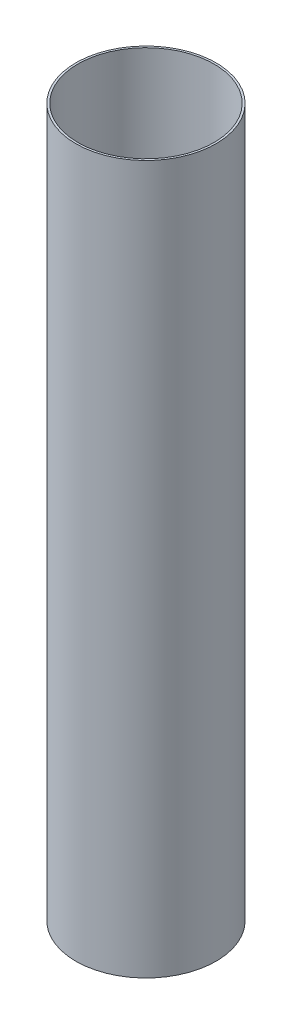
SolidWorks part; units mm, degrees
ref_plane "Front Plane" through (0, 0, 0) normal (0, 0, 1) x (1, 0, 0)
ref_plane "Top Plane" through (0, 0, 0) normal (0, 1, 0) x (1, 0, 0)
ref_plane "Right Plane" through (0, 0, 0) normal (1, 0, 0) x (0, 0, -1)
sketch "Sketch1" plane through (0, 0, 0) normal (0, 1, 0) x (1, 0, 0)
  circle A0 centre (0, 0) radius 65.405
  circle A1 centre (0, 0) radius 63.5
  dimension "D1" = 130.81
  dimension "D2" = 127
extrude "Boss-Extrude1" add sketch "Sketch1" along normal mid plane 660.4
equation "\"iDiameter\"= 5in"
equation "\"oDiameter\"= 5.15in"
equation "\"length\"= 26in"
